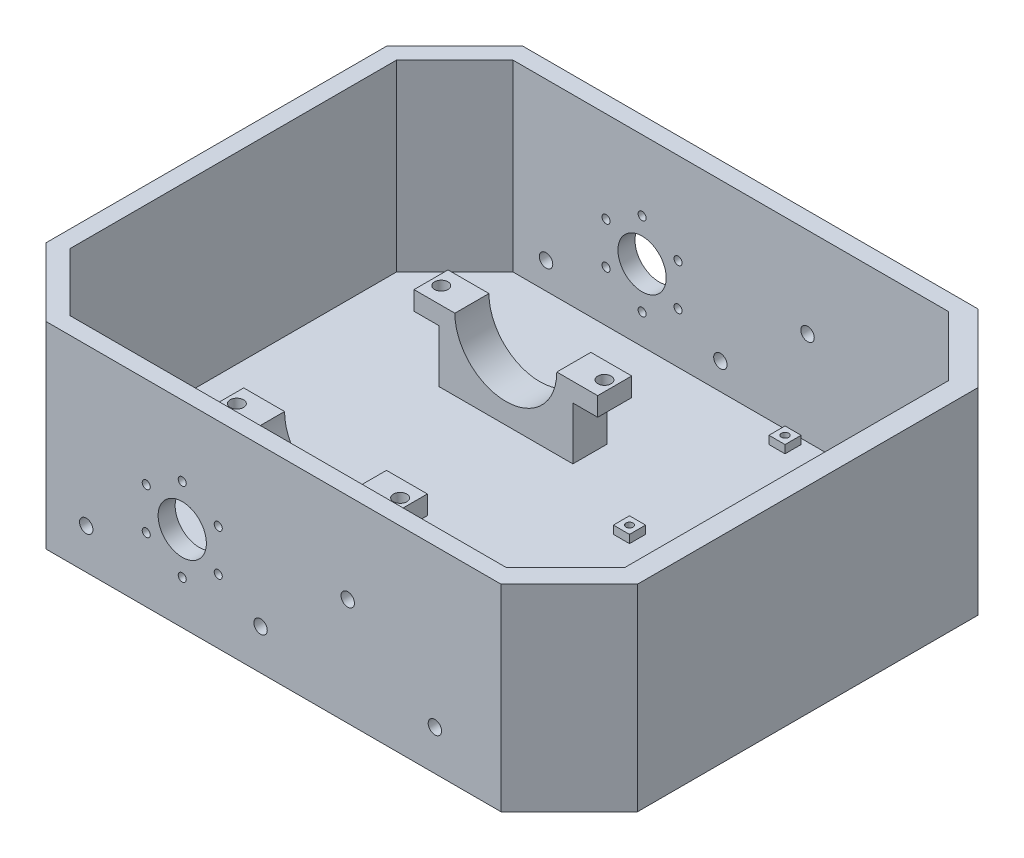
SolidWorks part; units mm, degrees
ref_plane "Front Plane" through (0, 0, 0) normal (0, 0, 1) x (1, 0, 0)
ref_plane "Top Plane" through (0, 0, 0) normal (0, 1, 0) x (1, 0, 0)
ref_plane "Right Plane" through (0, 0, 0) normal (1, 0, 0) x (0, 0, -1)
sketch "Sketch2" plane through (0, 0, 0) normal (0, 1, 0) x (1, 0, 0)
  line L1 (-127, 76.2) -> (63.5, 76.2)
  line L2 (-127, 76.2) -> (-127, -101.6)
  line L3 (-127, -101.6) -> (63.5, -101.6)
  line L4 (63.5, 76.2) -> (63.5, -101.6)
  dimension "D1" = 190.5
  dimension "D2" = 177.8
  dimension "D3" = 76.2
  dimension "D4" = 63.5
extrude "Boss-Extrude1" add sketch "Sketch2" along normal blind 5.08
chamfer "Chamfer1" distance 25.4 angle 45 2 edges at (-127, 2.54, -76.2) (-127, 2.54, 101.6)
sketch "Sketch4" plane through (0, 5.08, 0) normal (0, 1, 0) x (1, 0, 0)
  line L0 (57.15, 69.85) -> (-98.9697, 69.85)
  line L1 (-98.9697, 69.85) -> (-120.65, 48.1697)
  line L2 (-120.65, 48.1697) -> (-120.65, -73.5697)
  line L3 (-120.65, -73.5697) -> (-98.9697, -95.25)
  line L4 (-98.9697, -95.25) -> (57.15, -95.25)
  line L6 (63.5, 76.2) -> (-101.6, 76.2)
  line L7 (-101.6, 76.2) -> (-127, 50.8)
  line L8 (-127, 50.8) -> (-127, -76.2)
  line L9 (-127, -76.2) -> (-101.6, -101.6)
  line L10 (-101.6, -101.6) -> (63.5, -101.6)
  line L11 (63.5, -101.6) -> (63.5, 76.2)
  line L12 (63.5, 76.2) -> (-101.6, 76.2)
  line L13 (-101.6, 76.2) -> (-127, 50.8)
  line L14 (-127, 50.8) -> (-127, -76.2)
  line L15 (-127, -76.2) -> (-101.6, -101.6)
  line L16 (-101.6, -101.6) -> (63.5, -101.6)
  line L17 (63.5, -101.6) -> (63.5, -95.25)
  line L18 (57.15, 69.85) -> (63.5, 69.85)
  line L19 (57.15, -95.25) -> (63.5, -95.25)
  line L20 (63.5, 69.85) -> (63.5, 76.2)
  line L21 (63.5, -101.6) -> (63.5, 76.2) construction
  line L22 (57.15, -95.25) -> (57.15, 69.85) construction
  dimension "D2" = 6.35
  dimension "D1" = 0
extrude "Boss-Extrude3" add sketch "Sketch4" along normal blind 68.42
sketch "Sketch5" plane through (0, 0, 101.6) normal (0, 0, 1) x (1, 0, 0)
  line L0 (-150.3871, 38.1) -> (157.7429, 38.1) construction
  line L1 (-101.6, 0) -> (63.5, 0) construction
  line L2 (0, -14.9262) -> (0, 83.7522) construction
  line L3 (-50.8, 49.8289) -> (-50.8, 11.4994) construction
  line L5 (-71.0506, 31.75) -> (-33.7726, 31.75) construction
  circle A0 centre (-50.8, 31.75) radius 9
  circle A1 centre (-50.8, 31.75) radius 15.5 construction
  circle A2 centre (-50.8, 47.25) radius 1.5
  circle A3 centre (-37.3766, 39.5) radius 1.5
  circle A4 centre (-37.3766, 24) radius 1.5
  circle A5 centre (-50.8, 16.25) radius 1.5
  circle A6 centre (-64.2234, 24) radius 1.5
  circle A7 centre (-64.2234, 39.5) radius 1.5
  dimension "D2" = 18
  dimension "D5" = 31
  dimension "D6" = 3
  dimension "D1" = 38.1
  dimension "D3" = 50.8
  dimension "D4" = 6.35
  dimension "D7" = 6
extrude "Cut-Extrude1" cut sketch "Sketch5" against normal through all
sketch "Sketch10" plane through (63.5, 0, 0) normal (1, 0, 0) x (0, 0, -1)
  line L1 (-101.6, 0) -> (76.2, 0)
  line L2 (-101.6, 0) -> (-101.6, 73.5)
  line L3 (-101.6, 73.5) -> (76.2, 73.5)
  line L4 (76.2, 0) -> (76.2, 73.5)
extrude "Boss-Extrude6" add sketch "Sketch10" along normal blind 30
chamfer "Chamfer3" distance 25.4 angle 45 2 edges at (93.5, 36.75, -76.2) (93.5, 36.75, 101.6)
sketch "Sketch11" plane through (0, 73.5, 0) normal (0, 1, 0) x (1, 0, 0)
  line L0 (63.5, -95.25) -> (85.7572, -72.9928)
  line L1 (85.7572, -72.9928) -> (85.7572, 47.5928)
  line L2 (85.7572, 47.5928) -> (63.5, 69.85)
  line L4 (63.5, -95.25) -> (63.5, 69.85)
  line L5 (85.7572, 47.5928) -> (62.625, 70.725) construction
  line L6 (62.625, -96.125) -> (85.7572, -72.9928) construction
  line L8 (93.5, -76.2) -> (93.5, 50.8)
  line L9 (93.5, 50.8) -> (68.1, 76.2)
  line L10 (68.1, 76.2) -> (-101.6, 76.2)
  line L11 (-101.6, 76.2) -> (-127, 50.8)
  line L12 (-127, 50.8) -> (-127, -76.2)
  line L13 (-127, -76.2) -> (-101.6, -101.6)
  line L14 (-101.6, -101.6) -> (68.1, -101.6)
  line L15 (68.1, -101.6) -> (93.5, -76.2)
  line L16 (93.5, -76.2) -> (93.5, 50.8)
  line L17 (93.5, 50.8) -> (68.1, 76.2)
  line L23 (68.1, -101.6) -> (93.5, -76.2)
  line M22 (63.5, 69.85) -> (63.5, -95.25)
  dimension "D1" = 0
extrude "Cut-Extrude2" cut sketch "Sketch11" along direction (0, 1, 0) on the side against the normal up to surface (68.42 mm away) contours L1 L2 L0 M22 region at (74.0506, 73.5, 12.7) up to face at (-52.0399, 5.08, 12.7)
sketch "Sketch12" plane through (0, 0, 95.25) normal (0, 0, -1) x (-1, 0, 0)
  line L1 (-63.5, 5.08) -> (98.9697, 5.08) construction
  line L2 (25.8, 5.08) -> (75.8, 5.08)
  line L3 (25.8, 5.08) -> (25.8, 31.75)
  line L4 (25.8, 31.75) -> (31.8, 31.75)
  line L5 (75.8, 5.08) -> (75.8, 31.75)
  line L6 (69.8, 31.75) -> (75.8, 31.75)
  arc A0 (31.8, 31.75) -> (69.8, 31.75) centre (50.8, 31.75) ccw
  dimension "D1" = 38
  dimension "D2" = 25
  dimension "D3" = 25
extrude "Boss-Extrude7" add sketch "Sketch12" along normal blind 12.7 from offset 38.1
ref_plane "Plane1" through (0, 0, 12.7) normal (0, 0, 1) x (1, 0, 0)
sketch "Sketch13" plane through (0, 31.75, 0) normal (0, 1, 0) x (1, 0, 0)
  line L0 (-25.8, -44.45) -> (-75.8, -44.45) construction
  line L1 (-31.8, -44.45) -> (-16.56, -44.45)
  line L2 (-31.8, -44.45) -> (-31.8, -57.15)
  line L3 (-31.8, -57.15) -> (-16.56, -57.15)
  line L4 (-16.56, -44.45) -> (-16.56, -57.15)
  line L5 (-31.8, -44.45) -> (-25.8, -44.45) construction
  line L6 (-31.8, -57.15) -> (-25.8, -57.15) construction
  line L7 (-31.8, -44.45) -> (-31.8, -57.15) construction
  dimension "D1" = 15.24
extrude "Boss-Extrude8" add sketch "Sketch13" against normal blind 7
sketch "Sketch14" plane through (0, 31.75, 0) normal (0, 1, 0) x (1, 0, 0)
  line L0 (-31.8, -44.45) -> (-16.56, -44.45) construction
  line L2 (-20.37, -50.8) -> (-20.37, -44.45) construction
  line L3 (-20.37, -50.8) -> (-20.37, -57.15) construction
  line L4 (-31.8, -57.15) -> (-16.56, -57.15) construction
  line L5 (-31.8, -44.45) -> (-31.8, -57.15) construction
  circle A0 centre (-20.37, -50.8) radius 2.5
  dimension "D1" = 5
  dimension "D2" = 11.43
extrude "Cut-Extrude3" cut sketch "Sketch14" against normal blind 10
ref_plane "Plane2" through (-50.8, 0, 0) normal (-1, 0, 0) x (0, 0, 1)
mirror "Mirror2" about plane through (-50.8, 0, 0) normal (-1, 0, 0) of "Boss-Extrude8"
mirror "Mirror3" about plane through (-50.8, 0, 0) normal (-1, 0, 0) of "Cut-Extrude3"
mirror "Mirror4" about plane through (0, 0, 12.7) normal (0, 0, 1) of "Boss-Extrude7", "Boss-Extrude8", "Cut-Extrude3", "Mirror3", "Mirror2"
sketch "Sketch15" plane through (0, 0, 101.6) normal (0, 0, 1) x (1, 0, 0)
  line L0 (-101.6, 0) -> (68.1, 0) construction
  line L1 (-101.6, 73.5) -> (-101.6, 0) construction
  circle A0 centre (-86.6, 15) radius 2.5
  circle A1 centre (-21.6, 15) radius 2.5
  circle A2 centre (43.4, 15) radius 2.5
  circle A3 centre (10.9, 40) radius 2.5
  point P8 (0, 0)
  point P11 (-7.8284, 19.519)
  point P12 (0, 0)
  dimension "D1" = 5
  dimension "D2" = 40
  dimension "D4" = 65
  dimension "D5" = 15
  dimension "D6" = 15
  dimension "D3" = 130
  dimension "D7" = 32.5
extrude "Cut-Extrude4" cut sketch "Sketch15" against normal through all contours A1 | A3 | A2 | A0 region at (-21.6, 15, 101.6) region at (43.4, 15, 101.6) region at (10.9, 40, 101.6)
sketch "Sketch17" plane through (0, 5.08, 0) normal (0, 1, 0) x (1, 0, 0)
  line L0 (-98.9697, 69.85) -> (63.5, 69.85) construction
  line L1 (4.5, 67.85) -> (10.5, 67.85)
  line L2 (4.5, 67.85) -> (4.5, 61.85)
  line L3 (4.5, 61.85) -> (10.5, 61.85)
  line L4 (10.5, 67.85) -> (10.5, 61.85)
  line L5 (4.5, 67.85) -> (10.5, 61.85) construction
  line L6 (4.5, 61.85) -> (10.5, 67.85) construction
  line L7 (59.5, 61.85) -> (53.5, 61.85)
  line L8 (59.5, 61.85) -> (59.5, 67.85)
  line L9 (59.5, 67.85) -> (53.5, 67.85)
  line L10 (53.5, 61.85) -> (53.5, 67.85)
  line L11 (59.5, 61.85) -> (53.5, 67.85) construction
  line L12 (59.5, 67.85) -> (53.5, 61.85) construction
  line L13 (4.5, 9.85) -> (10.5, 9.85)
  line L14 (4.5, 9.85) -> (4.5, 3.85)
  line L15 (4.5, 3.85) -> (10.5, 3.85)
  line L16 (10.5, 9.85) -> (10.5, 3.85)
  line L17 (4.5, 9.85) -> (10.5, 3.85) construction
  line L18 (4.5, 3.85) -> (10.5, 9.85) construction
  line L19 (53.5, 9.85) -> (59.5, 9.85)
  line L20 (53.5, 9.85) -> (53.5, 3.85)
  line L21 (53.5, 3.85) -> (59.5, 3.85)
  line L22 (59.5, 9.85) -> (59.5, 3.85)
  line L23 (53.5, 9.85) -> (59.5, 3.85) construction
  line L24 (53.5, 3.85) -> (59.5, 9.85) construction
  circle A0 centre (7.5, 64.85) radius 1.35
  circle A1 centre (56.5, 64.85) radius 1.35
  circle A2 centre (7.5, 6.85) radius 1.35
  circle A3 centre (56.5, 6.85) radius 1.35
  dimension "D3" = 2.7
  dimension "D1" = 58
  dimension "D2" = 49
  dimension "D4" = 6
  dimension "D5" = 5
  dimension "D6" = 4
extrude "Boss-Extrude9" add sketch "Sketch17" along normal blind 3
